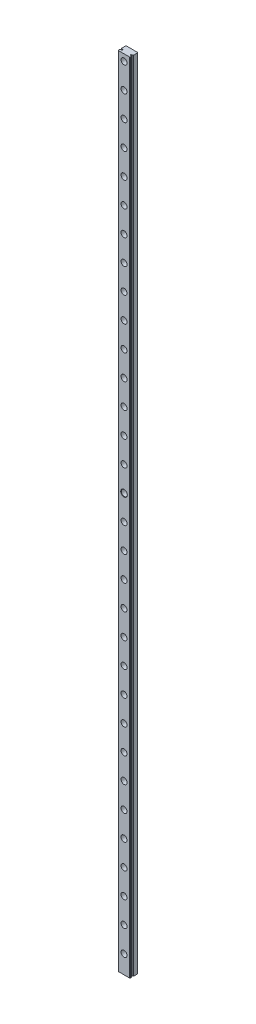
SolidWorks part; units mm, degrees
material "Alloy Steel (SS)"
ref_plane "Horní rovina" through (0, 0, 0) normal (0, 0, 1) x (1, 0, 0)
ref_plane "Přední rovina" through (0, 0, 0) normal (0, 1, 0) x (1, 0, 0)
ref_plane "Pravá rovina" through (0, 0, 0) normal (1, 0, 0) x (0, 0, -1)
sketch "Skica1" plane through (0, 0, 0) normal (0, 1, 0) x (1, 0, 0)
  line L0 (-5.5, -8) -> (5.5, -8)
  line L2 (6, -7.5) -> (6, -6.6619)
  line L3 (5.2091, -6) -> (4, -5.95)
  line L4 (4, -5.95) -> (4, -5.05)
  line L5 (4, -5.05) -> (5.2091, -5)
  line L6 (6, -4.3381) -> (6, -0.5)
  line L8 (5.5, 0) -> (-1.6, 0)
  line L9 (-2.4, 0) -> (-5.5, 0)
  line L11 (-6, -0.5) -> (-6, -4.3381)
  line L12 (-5.2091, -5) -> (-4, -5.05)
  line L13 (-4, -5.05) -> (-4, -5.95)
  line L14 (-4, -5.95) -> (-5.2091, -6)
  line L15 (-6, -6.6619) -> (-6, -7.5)
  line L17 (0, -9.4784) -> (0, 1.3023) construction
  line L18 (5.5, -8) -> (6, -7.5)
  line L19 (-6, -7.5) -> (-5.5, -8)
  line L20 (-5.5, 0) -> (-6, -0.5)
  line L21 (6, -0.5) -> (5.5, 0)
  line L22 (4, -5.5) -> (-4, -5.5) construction
  arc A0 (5.2091, -6) -> (6, -6.6619) centre (6.3, -5.5) ccw
  arc A1 (6, -4.3381) -> (5.2091, -5) centre (6.3, -5.5) ccw
  arc A2 (-2.4, 0) -> (-1.6, 0) centre (-2, 0.3) ccw
  arc A5 (-6, -4.3381) -> (-5.2091, -5) centre (-6.3, -5.5) cw
  arc A6 (-5.2091, -6) -> (-6, -6.6619) centre (-6.3, -5.5) cw
  point P0 (-6, -8)
  point P1 (6, -8)
  point P14 (6, 0)
  point P19 (-6, 0)
  dimension "D4" = 1.2
  dimension "D18" = 0.5
  dimension "D1" = 6
  dimension "D3" = 8
  dimension "D5" = 6.3
  dimension "D6" = 5.5
  dimension "D7" = 4
  dimension "D8" = 4
  dimension "D13" = 0.9
  dimension "D14" = 0.9
  dimension "D15" = 5.5
  dimension "D16" = 1
  dimension "D17" = 0.5
  dimension "D19" = 2
  dimension "D20" = 0.3
  dimension "D9" = 0.5
  dimension "D10" = 0.5
  dimension "D11" = 0.5
  dimension "D12" = 0.5
  dimension "D21" = 0.5
  dimension "D22" = 0.5
  dimension "D23" = 0.5
  dimension "D24" = 0.5
  dimension "D25" = 6
extrude "Delka" add sketch "Skica1" along normal blind 362.75
sketch "Sketch1" plane through (0, 0, 0) normal (0, -1, 0) x (1, 0, 0)
  line L17 (6, 6.6619) -> (6, 7.5)
  line L18 (6, 7.5) -> (5.5, 8)
  line L19 (5.5, 8) -> (-5.5, 8)
  line L20 (-5.5, 8) -> (-6, 7.5)
  line L21 (-6, 7.5) -> (-6, 6.6619)
  line L22 (-5.2091, 6) -> (-4, 5.95)
  line L23 (-4, 5.95) -> (-4, 5.05)
  line L24 (-4, 5.05) -> (-5.2091, 5)
  line L25 (-6, 4.3381) -> (-6, 0.5)
  line L26 (-6, 0.5) -> (-5.5, 0)
  line L27 (-5.5, 0) -> (-2.4, 0)
  line L28 (-1.6, 0) -> (5.5, 0)
  line L29 (5.5, 0) -> (6, 0.5)
  line L30 (6, 0.5) -> (6, 4.3381)
  line L31 (5.2091, 5) -> (4, 5.05)
  line L32 (4, 5.05) -> (4, 5.95)
  line L33 (4, 5.95) -> (5.2091, 6)
  line L34 (6, 6.6619) -> (6, 7.5)
  line L35 (6, 7.5) -> (5.5, 8)
  line L36 (5.5, 8) -> (-5.5, 8)
  line L37 (-5.5, 8) -> (-6, 7.5)
  line L38 (-6, 7.5) -> (-6, 6.6619)
  line L39 (-5.2091, 6) -> (-4, 5.95)
  line L40 (-4, 5.95) -> (-4, 5.05)
  line L41 (-4, 5.05) -> (-5.2091, 5)
  line L42 (-6, 4.3381) -> (-6, 0.5)
  line L43 (-6, 0.5) -> (-5.5, 0)
  line L44 (-5.5, 0) -> (-2.4, 0)
  line L45 (-1.6, 0) -> (5.5, 0)
  line L46 (5.5, 0) -> (6, 0.5)
  line L47 (6, 0.5) -> (6, 4.3381)
  line L48 (5.2091, 5) -> (4, 5.05)
  line L49 (4, 5.05) -> (4, 5.95)
  line L50 (4, 5.95) -> (5.2091, 6)
  arc A5 (6, 6.6619) -> (5.2091, 6) centre (6.3, 5.5) ccw
  arc A6 (-5.2091, 6) -> (-6, 6.6619) centre (-6.3, 5.5) ccw
  arc A7 (-6, 4.3381) -> (-5.2091, 5) centre (-6.3, 5.5) ccw
  arc A8 (-1.6, 0) -> (-2.4, 0) centre (-2, -0.3) ccw
  arc A9 (5.2091, 5) -> (6, 4.3381) centre (6.3, 5.5) ccw
  arc A10 (6, 6.6619) -> (5.2091, 6) centre (6.3, 5.5) ccw
  arc A11 (-5.2091, 6) -> (-6, 6.6619) centre (-6.3, 5.5) ccw
  arc A12 (-6, 4.3381) -> (-5.2091, 5) centre (-6.3, 5.5) ccw
  arc A13 (-1.6, 0) -> (-2.4, 0) centre (-2, -0.3) ccw
  arc A14 (5.2091, 5) -> (6, 4.3381) centre (6.3, 5.5) ccw
  dimension "D1" = 0
extrude "Boss-Extrude1" add sketch "Sketch1" along normal blind 437.25
hole_wizard "Díra1" positions "Skica3" profile "Skica4" legacy end condition through all
sketch "Skica3" plane through (0, 0, 8) normal (0, 0, 1) x (1, 0, 0)
  point P0 (0, -18.875)
  point P2 (0, -18.875)
  dimension "D1" = 18.875
sketch "Skica4" plane through (0, -18.875, 8) normal (1, 0, 0) x (0, -1, 0)
  line L0 (0, 0) -> (0, 8)
  line L1 (0, 8) -> (1.75, 8)
  line L2 (1.75, 8) -> (1.75, 4.5)
  line L3 (1.75, 4.5) -> (3, 4.5)
  line L4 (3, 4.5) -> (3, 0)
  line L5 (3, 0) -> (0, 0)
  line L6 (0, 110) -> (0, -10) construction
  dimension "Průměr" = 3.5
  dimension "Hloubka" = 8
  dimension "Průměr válc. zahloubení" = 6
  dimension "Hloubka válc. zahloubení" = 4.5
chamfer "Zkosení1" distance 0.3 angle 45 2 edges at (1.75, -18.875, 0) (3, -18.875, 8)
pattern_linear "LPattern1" count 17 spacing 25 along (0, -1, 0) count 16 spacing 25 along (0, 1, 0) of "Díra1" pattern seed only yes
equation "\"D17@Skica1\"=\"D16@Skica1\"/2"
equation "\"D10@Skica1\"=\"D9@Skica1\""
equation "\"D11@Skica1\"=\"D9@Skica1\""
equation "\"D12@Skica1\"=\"D9@Skica1\""
equation "\"D21@Skica1\"=\"D9@Skica1\""
equation "\"D22@Skica1\"=\"D9@Skica1\""
equation "\"D23@Skica1\"=\"D9@Skica1\""
equation "\"D24@Skica1\"=\"D9@Skica1\""
equation "\"P\"= 25mm"
equation "\"Emin\"= 5mm"
equation "\"Emax\"= 20mm"
equation "\"Hc\"= round (  ( \"D1@Delka\" - 2 * \"Emin\" )  / \"P\" ) "
equation "\"E\"= ( \"L\" - ( ( \"Hc\" - 1 ) * \"P\" ) ) / 2"
equation "\"L\"=362.75"
equation "\"D1@Delka\" = \"L\""
equation "\"D1\"= \"Hc\""
equation "\"D3\"= \"P\""
equation "\"D1@Skica3\"= \"E\""
equation "\"D25@Skica1\"=\"D1@Skica1\""
equation "\"Přidat vysunutím1\"= \"L\""
equation "\"Delka\"= \"L\""
